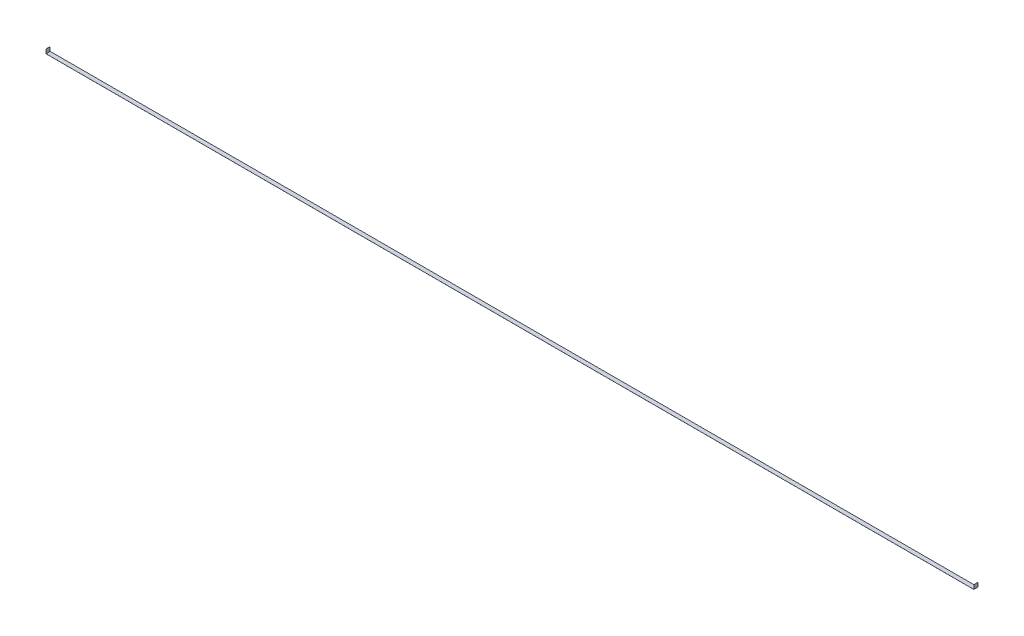
SolidWorks part; units mm, degrees
material "Nylon 101"
ref_plane "Front Plane" through (0, 0, 0) normal (0, 0, 1) x (1, 0, 0)
ref_plane "Top Plane" through (0, 0, 0) normal (0, 1, 0) x (1, 0, 0)
ref_plane "Right Plane" through (0, 0, 0) normal (1, 0, 0) x (0, 0, -1)
sketch "Sketch1" plane through (0, 0, 0) normal (0, 0, 1) x (1, 0, 0)
  line L0 (-2832.1, 0) -> (2832.1, 0)
  line L1 (2832.1, 0) -> (2832.1, 25.4)
  line L3 (-2832.1, 25.4) -> (-2832.1, 0)
  point P4 (0, 0)
  dimension "D1" = 25.4
  dimension "D2" = 5664.2
extrude "Extrude-Thin1" add sketch "Sketch1" along normal blind 25.4 thin thin type one direction wall 0.254
